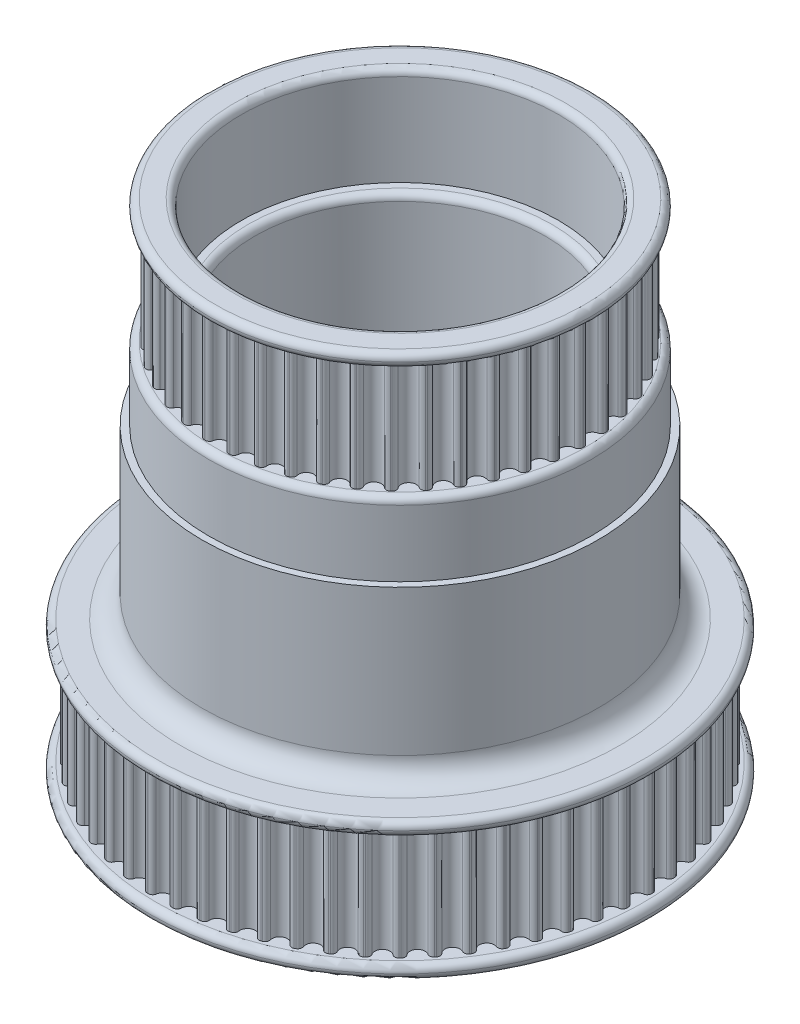
SolidWorks part; units mm, degrees
ref_plane "Front Plane" through (0, 0, 0) normal (0, 0, 1) x (1, 0, 0)
ref_plane "Top Plane" through (0, 0, 0) normal (0, 1, 0) x (1, 0, 0)
ref_plane "Right Plane" through (0, 0, 0) normal (1, 0, 0) x (0, 0, -1)
sketch "PulleyOffsets" plane through (0, 0, 0) normal (1, 0, 0) x (0, 0, -1)
  line L0 (21.4312, 0) -> (-21.4312, 0) construction
  line L1 (21.4312, 42.8625) -> (-21.4312, 42.8625) construction
  line L2 (0, 0) -> (0, 42.8625) construction
  point P7 (0, 0)
  dimension "D1" = 42.8625
ref_axis "Axis1" through (0, 34.9332, 0) along (0, -1, 0)
ref_plane "Big Pulley Plane" through (0, 0, 0) normal (0, 1, 0) x (1, 0, 0)
ref_plane "Small Pulley Plane" through (0, 42.8625, 0) normal (0, 1, 0) x (1, 0, 0)
sketch "Sketch1" plane through (0, 0, 0) normal (0, 1, 0) x (1, 0, 0)
  line L0 (0, 0) -> (0, 28.2667) construction
  line L1 (0, 0) -> (2.9202, 27.7837) construction
  circle A0 centre (0, 0) radius 28.2667 construction
  circle A1 centre (0, 0) radius 27.0467 construction
  circle A2 centre (0, 27.9367) radius 0.89 construction
  circle A5 centre (2.9202, 27.7837) radius 0.89 construction
  arc A6 (0, 27.0467) -> (0.8804, 27.8061) centre (0, 27.9367) ccw
  arc A7 (0.8804, 27.8061) -> (1.3997, 28.2321) centre (1.3749, 27.7327) cw
  arc A8 (1.559, 28.2237) -> (2.031, 27.7458) centre (1.5314, 27.7245) cw
  arc A9 (2.8272, 26.8986) -> (2.031, 27.7458) centre (2.9202, 27.7837) cw
  arc A10 (1.3997, 28.2321) -> (1.559, 28.2237) centre (0, 0) cw
  arc A11 (0, 27.0467) -> (2.8272, 26.8986) centre (0, 0) ccw
  dimension "D1" = 56.5335
  dimension "D3" = 1.78
  dimension "D4" = 0.5
  dimension "D2" = 1.22
  dimension "D5" = 6
extrude "Boss-Extrude1" add sketch "Sketch1" along normal mid plane 13 contours A6 A11 A9 A8 A7 region at (0.001, 0, -0.0192)
pattern_circular "CirPattern1" count 60 over 360 about axis through (0, 34.9332, 0) along (0, -1, 0) of "Boss-Extrude1"
sketch "Sketch2" plane through (0, 0, 0) normal (1, 0, 0) x (0, 0, -1)
  line L10 (0, 6.5) -> (29.4415, 6.5) construction
  line L11 (0, 6.5) -> (0, 8.0875) construction
  line L12 (0, 8.0875) -> (29.4415, 8.0875) construction
  line L15 (29.4415, 6.5) -> (29.4415, 8.0875) construction
  line L20 (0, 34.9332) -> (0, -6.9932) construction
  line L22 (29.4415, 8.0875) -> (0, 8.0875)
  line L23 (29.4415, 8.0875) -> (29.4415, 6.5)
  line L24 (29.4415, 6.5) -> (0, 6.5)
  line L25 (0, 8.0875) -> (0, 6.5)
  dimension "D1" = 1.5875
  dimension "D2" = 29.4415
  dimension "D3" = 6.5
revolve "Revolve3" add sketch "Sketch2" angle 360 about axis through (0, 34.9332, 0) along (0, -1, 0) region at (0, 7.2937, -14.7207)
mirror "Mirror1" about plane through (0, 0, 0) normal (0, 1, 0) of "Revolve3"
sketch "Sketch6" plane through (0, 0, 0) normal (0, 1, 0) x (1, 0, 0)
  line L0 (0, 0) -> (0, 21.582) construction
  line L1 (0, 0) -> (2.8938, 21.0541) construction
  circle A0 centre (0, 0) radius 21.582 construction
  circle A1 centre (0, 0) radius 20.362 construction
  circle A2 centre (0, 21.252) radius 0.89 construction
  circle A5 centre (2.8938, 21.0541) radius 0.89 construction
  arc A6 (0, 20.362) -> (0.8793, 21.1145) centre (0, 21.252) ccw
  arc A7 (0.8793, 21.1145) -> (1.4059, 21.5362) centre (1.3733, 21.0373) cw
  arc A8 (1.5397, 21.527) -> (2.004, 21.0376) centre (1.5041, 21.0283) cw
  arc A9 (2.7726, 20.1724) -> (2.004, 21.0376) centre (2.8938, 21.0541) cw
  arc A10 (1.4059, 21.5362) -> (1.5397, 21.527) centre (0, 0) cw construction
  arc A11 (0, 20.362) -> (2.7726, 20.1724) centre (0, 0) ccw
  arc A12 (1.4059, 21.5362) -> (1.5397, 21.527) centre (0, 0) cw
  dimension "D3" = 1.78
  dimension "D4" = 0.5
  dimension "D2" = 1.22
  dimension "D1" = 43.1641
  dimension "D5" = 7.826
extrude "Boss-Extrude2" add sketch "Sketch6" along normal mid plane 13 from surface contours A6 A11 A9 A8 A7 region at (0.0017, 0, -0.025) starting at plane "Small Pulley Plane"
pattern_circular "CirPattern2" count 46 over 360 about axis through (0, 34.9332, 0) along (0, -1, 0) of "Boss-Extrude2"
sketch "Sketch9" plane through (0, 0, 0) normal (1, 0, 0) x (0, 0, -1)
  line L1 (0, 36.3625) -> (22.7568, 36.3625)
  line L2 (0, 36.3625) -> (0, 34.775)
  line L3 (0, 34.775) -> (22.7568, 34.775)
  line L4 (22.7568, 36.3625) -> (22.7568, 34.775)
  line L6 (0, 49.3625) -> (22.7568, 49.3625)
  line L7 (0, 49.3625) -> (0, 50.95)
  line L8 (0, 50.95) -> (22.7568, 50.95)
  line L9 (22.7568, 49.3625) -> (22.7568, 50.95)
  line L10 (29.4415, 8.0875) -> (29.4415, 6.5) construction
  line L11 (0, 34.9332) -> (0, -6.9932) construction
  line L12 (21.1145, 49.3625) -> (20.362, 49.3625) construction
  line L13 (20.1641, 36.3625) -> (21.0376, 36.3625) construction
  dimension "D1" = 22.7568
revolve "Revolve4" add sketch "Sketch9" angle 360 about axis through (0, 34.9332, 0) along (0, -1, 0)
sketch "Sketch10" plane through (0, -8.0875, 0) normal (0, -1, 0) x (1, 0, 0)
  circle A0 centre (0, 0) radius 18.669
  dimension "D1" = 37.338
extrude "Cut-Extrude1" cut sketch "Sketch10" against normal through all
sketch "Sketch11" plane through (0, 50.95, 0) normal (0, 1, 0) x (1, 0, 0)
  circle A0 centre (0, 0) radius 22.5
  dimension "D1" = 45
extrude "Cut-Extrude2" cut sketch "Sketch11" against normal up to surface (16.175 mm away) flip side to cut up to face at (0, 34.775, 18.669)
sketch "Sketch12" plane through (0, 0, 0) normal (0, 0, 1) x (1, 0, 0)
  line L0 (29.4415, 8.0875) -> (-29.4415, 8.0875) construction
  line L1 (18.669, 34.775) -> (22.5, 34.775)
  line L2 (18.669, 34.775) -> (18.669, 8.0875) construction
  line L3 (18.669, 8.0875) -> (22.5, 8.0875)
  line L4 (22.5, 34.775) -> (22.5, 8.0875) construction
  line L5 (22.5, 34.775) -> (22.5, 36.3625) construction
  line L6 (22.5, 27.775) -> (22.5, 34.775)
  line L7 (22.5, 27.775) -> (23.2938, 27.775)
  line L8 (22.5, 27.775) -> (22.5, 8.0875) construction
  line L9 (22.5, 8.0875) -> (23.2938, 8.0875)
  line L10 (23.2938, 27.775) -> (23.2938, 8.0875)
  line L11 (18.669, -8.0875) -> (18.669, 8.0875) construction
  line L12 (18.669, 2.0875) -> (17.0815, 2.0875)
  line L13 (18.669, 2.0875) -> (18.669, 39.3625) construction
  line L14 (18.669, 39.3625) -> (17.0815, 39.3625)
  line L15 (17.0815, 2.0875) -> (17.0815, 39.3625)
  line L16 (-29.4415, -8.0875) -> (29.4415, -8.0875) construction
  line L18 (18.669, 2.0875) -> (18.669, 8.0875)
  line L19 (18.669, 34.775) -> (18.669, 39.3625)
  line L20 (220.55, 42.8625) -> (-220.55, 42.8625) construction
  dimension "D1" = 7
  dimension "D2" = 0.7937
  dimension "D3" = 10.175
  dimension "D5" = 1.5875
  dimension "D4" = 3.5
revolve "Revolve5" add sketch "Sketch12" angle 360 about axis through (0, 34.9332, 0) along (0, -1, 0)
fillet "Fillet1" radius 2.54 1 edges at (0, 8.0875, -23.2938)
fillet "Fillet2" radius 0.7937 11 edges at (0, 39.3625, 17.0815) (0, 50.95, -18.669) (0, -8.0875, -18.669) (0, 2.0875, 17.0815) (0, -8.0875, 29.4415) (0, 8.0875, 29.4415) (0, 50.95, 22.5) (0, 49.3625, 22.5) (0, 36.3625, -22.5) (0, 6.5, 29.4415) (0, -6.5, 29.4415)
sketch "Sketch13" plane through (0, -8.0875, 0) normal (0, -1, 0) x (1, 0, 0)
  circle A0 centre (0, 23.0188) radius 3.175
  dimension "D2" = 6.35
  dimension "D1" = 23.0188
extrude "Cut-Extrude3" cut sketch "Sketch13" against normal blind 3.175
equation "\"TEETH_NUM\"= 60"
equation "\"TOOTH_PITCH\"= 3mm"
equation "\"PITCH_LINE_OFFSET\"= .015in"
equation "\"DIAMETER_PER_GROOVE\"= \"OUTSIDE_DIAMETER\" / \"TEETH_NUM\" * 1in"
equation "\"PITCH_DIAMETER\"= ( ( \"TEETH_NUM\" * 3 - 1.31 ) / 3.1415 + .415 ) * 1mm"
equation "\"OUTSIDE_DIAMETER\"= \"PITCH_DIAMETER\" - \"PITCH_LINE_OFFSET\" * 2"
equation "\"D1@Sketch1\"=\"OUTSIDE_DIAMETER\""
equation "\"TOOTH_HEIGHT\"= 1.22mm"
equation "\"D2@Sketch1\"=\"TOOTH_HEIGHT\""
equation "\"TOOTH_DIAMETER\"= 1.78mm"
equation "\"INTERNAL_RADIUS\"= .5mm"
equation "\"D3@Sketch1\"=\"TOOTH_DIAMETER\""
equation "\"D5@Sketch1\"=360 / \"TEETH_NUM\""
equation "\"D4@Sketch1\"=\"INTERNAL_RADIUS\""
equation "\"D1@CirPattern1\"=\"TEETH_NUM\""
equation "\"BELT_GAP\"= 13mm"
equation "\"D2@Sketch2\"=\"PITCH_DIAMETER\"/2+1/32"
equation "\"D3@Sketch2\"=\"BELT_GAP\"/2"
equation "\"2_TEETH_NUM\"= 46"
equation "\"2_PITCH_DIAMETER\"= ( ( \"2_TEETH_NUM\" * 3 - 1.31 ) / 3.1415 + .415 ) * 1mm"
equation "\"2_OUTSIDE_DIAMETER\"= \"2_PITCH_DIAMETER\" - \"PITCH_LINE_OFFSET\" * 2"
equation "\"2_DIAMETER_PER_GROOVE\"= \"2_OUTSIDE_DIAMETER\" / \"2_TEETH_NUM\" * 1in"
equation "\"D5@Sketch6\"=360/\"2_TEETH_NUM\""
equation "\"D1@Sketch6\"=\"2_OUTSIDE_DIAMETER\""
equation "\"D2@Sketch6\"=\"TOOTH_HEIGHT\""
equation "\"D3@Sketch6\"=\"TOOTH_DIAMETER\""
equation "\"D4@Sketch6\"=\"INTERNAL_RADIUS\""
equation "\"2_BELT_GAP\"= 13mm"
equation "\"D1@CirPattern2\"=\"2_TEETH_NUM\""
equation "\"D1@Boss-Extrude2\"=\"2_BELT_GAP\""
equation "\"Pulley_OffSets\"= 1.75 - 1 / 16"
equation "\"D1@PulleyOffsets\" = \"Pulley_OffSets\""
equation "\"D1@Boss-Extrude1\"=\"BELT_GAP\""
equation "\"D1@Sketch9\"=\"2_PITCH_DIAMETER\"/2+1/32"
equation "\"bearing_hole_depth_arm_side\"= 7mm + .125in"
equation "\"D3@Sketch12\"=\"bearing_hole_depth_arm_side\""
